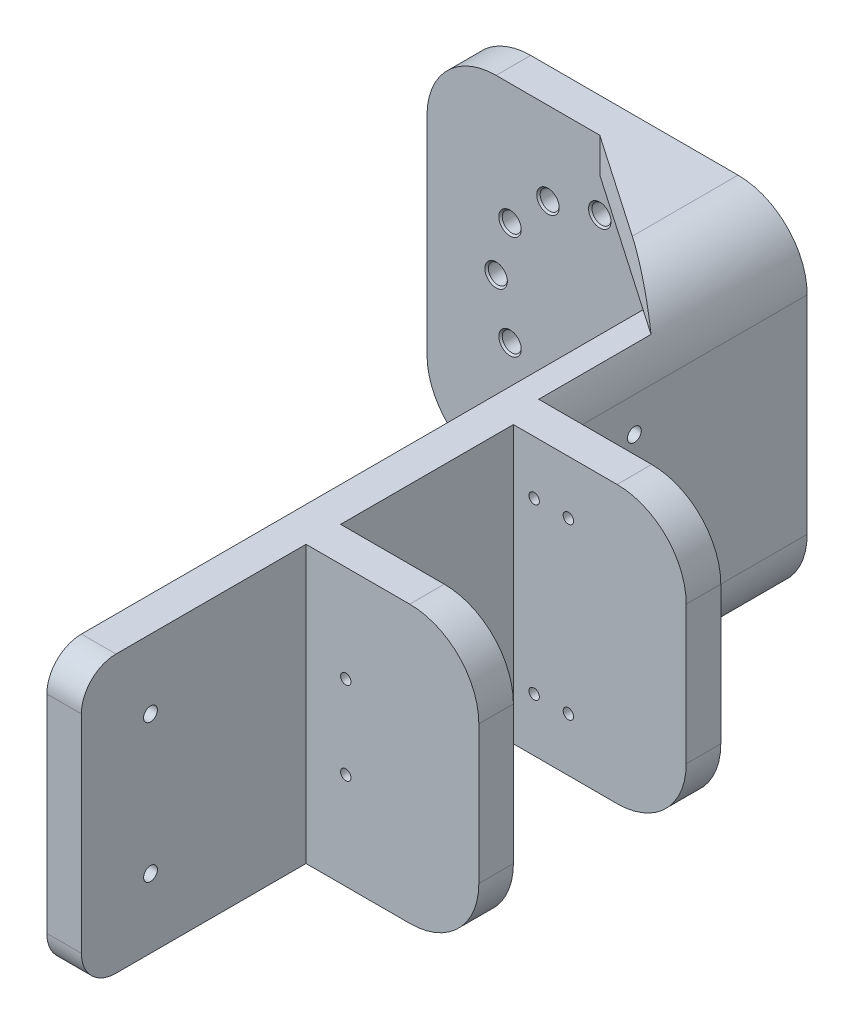
SolidWorks part; units mm, degrees
ref_plane "前视基准面" through (0, 0, 0) normal (0, 0, 1) x (1, 0, 0)
ref_plane "上视基准面" through (0, 0, 0) normal (0, 1, 0) x (1, 0, 0)
ref_plane "右视基准面" through (0, 0, 0) normal (1, 0, 0) x (0, 0, -1)
other "Configuration Table"
sketch "草图1" plane through (0, 0, 0) normal (1, 0, 0) x (0, 0, -1)
  line L1 (-100, 40) -> (100, 40)
  line L2 (-100, 40) -> (-100, -40)
  line L3 (-100, -40) -> (100, -40)
  line L4 (100, 40) -> (100, -40)
  dimension "D1" = 80
  dimension "D2" = 40
  dimension "D3" = 200
  dimension "D4" = 100
extrude "凸台-拉伸1" add sketch "草图1" along normal blind 10
sketch "草图2" plane through (10, 0, 0) normal (1, 0, 0) x (0, 0, -1)
  line L0 (100, 40) -> (-100, 40) construction
  line L1 (-35, 40) -> (-25, 40)
  line L2 (-35, 40) -> (-35, -40)
  line L3 (-35, -40) -> (-25, -40)
  line L4 (-25, 40) -> (-25, -40)
  line L5 (-100, -40) -> (100, -40) construction
  line L7 (25, 40) -> (35, 40)
  line L8 (25, 40) -> (25, -40)
  line L9 (25, -40) -> (35, -40)
  line L10 (35, 40) -> (35, -40)
  dimension "D1" = 10
  dimension "D2" = 10
  dimension "D3" = 50
  dimension "D4" = 25
extrude "凸台-拉伸2" add sketch "草图2" along normal blind 50
sketch "草图3" plane through (0, 0, -100) normal (0, 0, -1) x (-1, 0, 0)
  line L0 (0, -40) -> (0, 40) construction
  line L1 (-10, 50) -> (90, 50)
  line L2 (-10, 50) -> (-10, -50)
  line L3 (-10, -50) -> (90, -50)
  line L4 (90, 50) -> (90, -50)
  dimension "D1" = 100
  dimension "D2" = 50
  dimension "D3" = 50
  dimension "D4" = 10
extrude "凸台-拉伸3" add sketch "草图3" along normal blind 10
sketch "草图5" plane through (0, 40, 0) normal (0, 1, 0) x (1, 0, 0)
  line L0 (10, 55) -> (-15, 100)
  line L1 (10, 100) -> (10, 35) construction
  line L2 (-90, 100) -> (10, 100) construction
  line L3 (-15, 100) -> (10, 100)
  line L4 (10, 100) -> (10, 55)
  dimension "D1" = 45
  dimension "D2" = 25
extrude "凸台-拉伸4" add sketch "草图5" against normal blind 15
sketch "草图6" plane through (0, -40, 0) normal (0, -1, 0) x (1, 0, 0)
  line L3 (-15, -100) -> (0, -100)
  line L4 (0, -100) -> (0, -73)
  line L5 (0, -73) -> (-15, -100)
  line L6 (-15, -100) -> (0, -100)
  line L7 (0, -100) -> (0, -73)
  line L8 (0, -73) -> (-15, -100)
  dimension "D1" = 0
extrude "凸台-拉伸5" add sketch "草图6" against normal blind 15
fillet "圆角1" radius 20 4 edges at (10, 50, -105) (10, -50, -105) (-90, 50, -105) (-90, -50, -105)
sketch "草图7" plane through (0, 0, -110) normal (0, 0, -1) x (-1, 0, 0)
  line L0 (70, 50) -> (10, 50) construction
  line L1 (90, -30) -> (90, 30) construction
  circle A0 centre (40, 0) radius 30 construction
  circle A1 centre (40, 30) radius 2.75
  circle A2 centre (10, 0) radius 2.75
  circle A3 centre (70, 0) radius 2.75
  circle A4 centre (40, -30) radius 2.75
  dimension "D1" = 60
  dimension "D4" = 5.5
  dimension "D5" = 5.5
  dimension "D6" = 5.5
  dimension "D7" = 5.5
  dimension "D2" = 50
  dimension "50" = 50
extrude "切除-拉伸1" cut sketch "草图7" against normal blind 15
sketch "草图8" plane through (0, 0, -35) normal (0, 0, -1) x (-1, 0, 0)
  line L0 (-10, -30) -> (-10, 30) construction
  line L1 (-16, 24.5) -> (-25.9, 24.5) construction
  line L2 (-16, 24.5) -> (-16, -24.5) construction
  line L3 (-16, -24.5) -> (-25.9, -24.5) construction
  line L4 (-25.9, 24.5) -> (-25.9, -24.5) construction
  circle A0 centre (-16, 24.5) radius 1.5
  circle A1 centre (-25.9, 24.5) radius 1.5
  circle A2 centre (-16, -24.5) radius 1.5
  circle A3 centre (-25.9, -24.5) radius 1.5
  dimension "D5" = 3
  dimension "D1" = 9.9
  dimension "D2" = 49
  dimension "D3" = 24.5
  dimension "D4" = 6
extrude "切除-拉伸2" cut sketch "草图8" against normal blind 15
sketch "草图9" plane through (0, 0, 35) normal (0, 0, 1) x (1, 0, 0)
  line L0 (10, 40) -> (10, -40) construction
  circle A0 centre (21.5, 12) radius 1.5
  circle A1 centre (21.5, -12) radius 1.5
  dimension "D1" = 3
  dimension "D2" = 3
  dimension "D3" = 24
  dimension "D4" = 11.5
  dimension "D5" = 12
extrude "切除-拉伸3" cut sketch "草图9" against normal blind 15
fillet "圆角2" radius 20 4 edges at (60, -40, -30) (60, 40, -30) (60, -40, 30) (60, 40, 30)
sketch "草图16" plane through (0, 0, -100) normal (0, 0, 1) x (1, 0, 0)
  line L1 (-40, 0) -> (49960, 0) construction
  line L2 (-40, 0) -> (-40, 50000) construction
  line L3 (-40, 0) -> (24960, 43301.2702) construction
  line L4 (-40, 0) -> (43261.2702, 25000) construction
  line L5 (0, -25) -> (0, 25) construction
  circle A0 centre (-40, 0) radius 30 construction
  circle A1 centre (-25, 25.9808) radius 2.75
  circle A2 centre (-14.0192, 15) radius 2.75
  circle A3 centre (-25, -25.9808) radius 2.75
  circle A4 centre (-14.0192, -15) radius 2.75
  circle A5 centre (-55, 25.9808) radius 2.75
  circle A6 centre (-65.9808, 15) radius 2.75
  circle A7 centre (-55, -25.9808) radius 2.75
  circle A8 centre (-65.9808, -15) radius 2.75
  point P30 (-40, 0)
  dimension "D1" = 30
  dimension "D3" = 5.5
  dimension "D4" = 5.5
  dimension "D2" = 30
  dimension "D5" = 40
extrude "切除-拉伸7" cut sketch "草图16" against normal through all
chamfer "倒角2" distance 0.5 angle 45 12 edges at (-40, -27.25, -100) (-40, -27.25, -110) (-52.25, -25.9808, -100) (-52.25, -25.9808, -110) (-63.2308, -15, -100) (-63.2308, -15, -110) (-70, 2.75, -100) (-70, 2.75, -110) (-68.7308, 15, -100) (-68.7308, 15, -110) (-57.75, 25.9808, -100) (-57.75, 25.9808, -110)
chamfer "倒角3" distance 0.5 angle 45 12 edges at (-40, 32.75, -100) (-40, 32.75, -110) (-22.25, 25.9808, -100) (-22.25, 25.9808, -110) (-11.2692, 15, -100) (-11.2692, 15, -110) (-10, 2.75, -100) (-10, 2.75, -110) (-16.7692, -15, -100) (-16.7692, -15, -110) (-27.75, -25.9808, -100) (-27.75, -25.9808, -110)
sketch "草图17" plane through (0, -40, 0) normal (0, -1, 0) x (1, 0, 0)
  line L0 (7.3205, -100) -> (-40, -100)
  line L1 (-10, -100) -> (-70, -100) construction
  line L2 (-40, -100) -> (7.3205, -67.5)
  line L3 (7.3205, -100) -> (7.3205, -35) construction
  line L4 (7.3205, -67.5) -> (7.3205, -100)
extrude "凸台-拉伸8" add sketch "草图17" along normal blind 10
sketch "草图18" plane through (0, 0, -100) normal (0, 0, -1) x (-1, 0, 0)
  line L2 (-7.3205, -40) -> (-7.3205, -50)
  line L3 (-7.3205, -50) -> (10, -50)
  line L4 (-7.3205, -40) -> (-7.3205, -50)
  line L5 (-7.3205, -50) -> (10, -50)
  arc A1 (-7.3205, -40) -> (10, -50) centre (10, -30) ccw
  arc A2 (-7.3205, -40) -> (10, -50) centre (10, -30) ccw
  dimension "D1" = 0
extrude "切除-拉伸8" cut sketch "草图18" against normal through all
mirror "镜向2" about plane through (0, 0, 0) normal (0, 1, 0) of "凸台-拉伸8"
sketch "草图19" plane through (0, 0, -100) normal (0, 0, -1) x (-1, 0, 0)
  line L2 (-7.3205, 50) -> (-7.3205, 40)
  line L3 (10, 50) -> (-7.3205, 50)
  line L4 (-7.3205, 50) -> (-7.3205, 40)
  line L5 (10, 50) -> (-7.3205, 50)
  arc A1 (10, 50) -> (-7.3205, 40) centre (10, 30) ccw
  arc A2 (10, 50) -> (-7.3205, 40) centre (10, 30) ccw
  dimension "D1" = 0
extrude "切除-拉伸9" cut sketch "草图19" against normal through all
sketch "草图20" plane through (0, 0, 0) normal (-1, 0, 0) x (0, 0, 1)
  line L1 (-60, 20) -> (80, 20) construction
  line L2 (-60, 20) -> (-60, -20) construction
  line L3 (-60, -20) -> (80, -20) construction
  line L4 (80, 20) -> (80, -20) construction
  circle A0 centre (80, 20) radius 2
  circle A1 centre (80, -20) radius 2
  circle A2 centre (-60, 20) radius 2
  circle A3 centre (-60, -20) radius 2
  point P0 (0, 0)
  point P8 (69.1916, 21.9419)
  point P11 (0, 0)
  dimension "D1" = 4
  dimension "D2" = 4
  dimension "D3" = 4
  dimension "D4" = 4
  dimension "D5" = 40
  dimension "D6" = 20
  dimension "D7" = 140
  dimension "D8" = 60
extrude "切除-拉伸10" cut sketch "草图20" against normal through all
fillet "圆角3" radius 10 2 edges at (5, 40, 100) (5, -40, 100)
